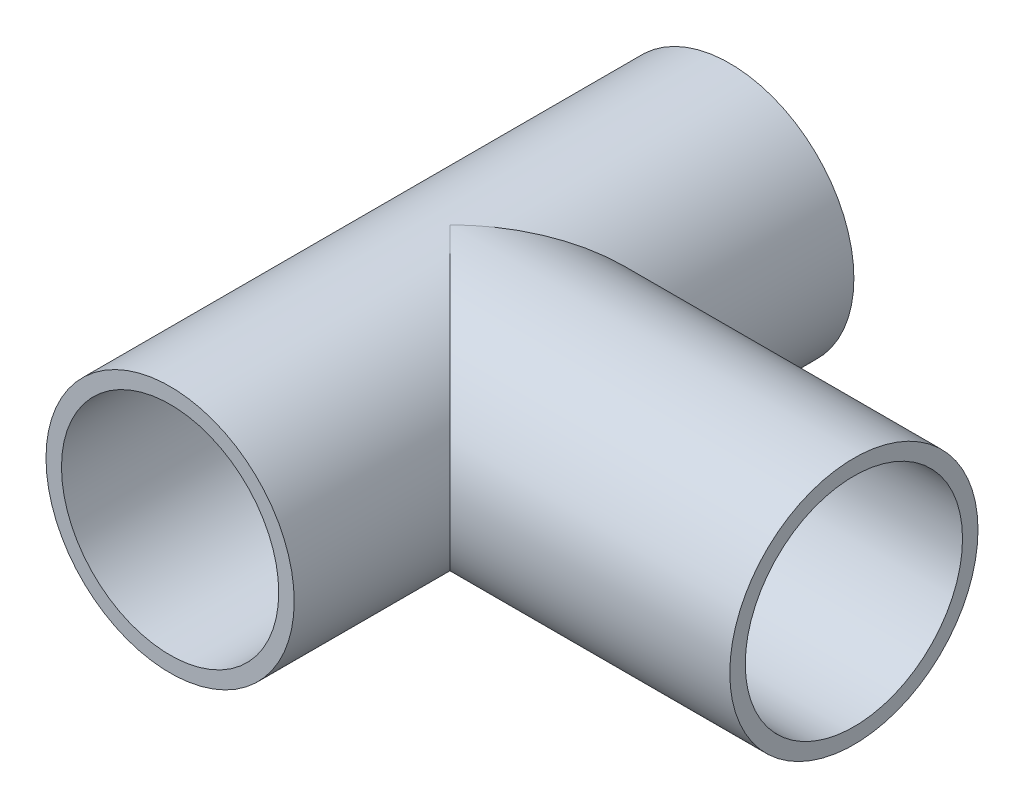
SolidWorks part; units mm, degrees
material "PE High Density"
ref_plane "Front Plane" through (0, 0, 0) normal (0, 0, 1) x (1, 0, 0)
ref_plane "Top Plane" through (0, 0, 0) normal (0, 1, 0) x (1, 0, 0)
ref_plane "Right Plane" through (0, 0, 0) normal (1, 0, 0) x (0, 0, -1)
sketch "Through Section" plane through (0, 0, 0) normal (0, 0, 1) x (1, 0, 0)
  circle A0 centre (0, 0) radius 161.925
  circle A1 centre (0, 0) radius 141.732
  dimension "D1" = 283.464
  dimension "D2" = 323.85
extrude "Through Section Extrude" add sketch "Through Section" along normal mid plane 730.25
ref_plane "E Plane" through (527.05, 0, 0) normal (1, 0, 0) x (0, 0, -1)
sketch "Orthogonal Section OD" plane through (527.05, 0, 0) normal (1, 0, 0) x (0, 0, -1)
  circle A0 centre (0, 0) radius 161.925
  point P2 (0, 0)
  point P4 (0, 0)
  point P5 (0, 0)
  point P6 (0, 0)
  dimension "D3" = 323.85
extrude "Orthogonal Section OD Extrude" add sketch "Orthogonal Section OD" against normal up to surface (365.125 mm away) up to face at (161.925, 0, 365.125)
sketch "Orthogonal Section ID" plane through (527.05, 0, 0) normal (1, 0, 0) x (0, 0, -1)
  circle A0 centre (0, 0) radius 141.732
  circle A1 centre (0, 0) radius 161.925 construction
  dimension "D1" = 283.464
extrude "Orthogonal Section ID Cut" cut sketch "Orthogonal Section ID" against normal up to surface (527.05 mm away) up to plane "Right Plane"
equation "\"ID\"= 11.160in'EPG"
equation "\"OD\"= 12.75'EPG"
equation "\"A\"= 8in'EPG"
equation "\"C\"= 28.75in'EPG"
equation "\"E\"= 8in'EPG"
equation "\"D1@Through Section\" = \"ID\""
equation "\"D2@Through Section\" = \"OD\""
equation "\"D1@Through Section Extrude\" = \"C\""
equation "\"D3@Orthogonal Section OD\" = \"OD\""
equation "\"D1@Orthogonal Section ID\" = \"ID\""
